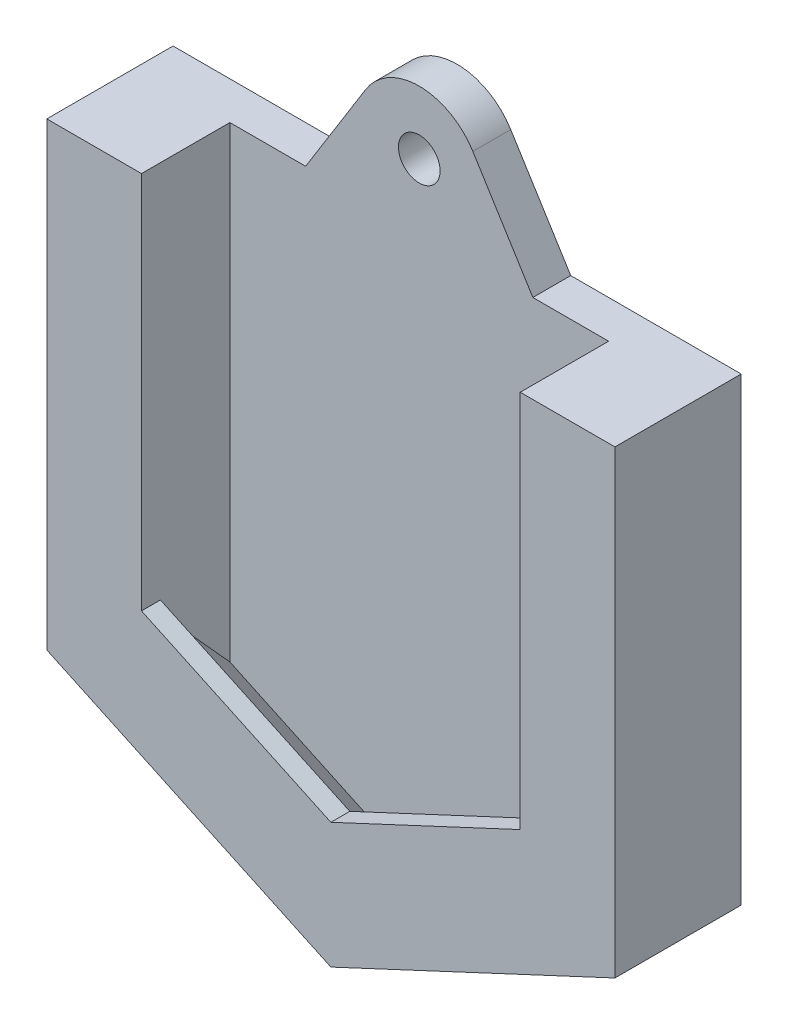
SolidWorks part; units mm, degrees
ref_plane "Plano frontal" through (0, 0, 0) normal (0, 0, 1) x (1, 0, 0)
ref_plane "Plano superior" through (0, 0, 0) normal (0, 1, 0) x (1, 0, 0)
ref_plane "Plano direito" through (0, 0, 0) normal (1, 0, 0) x (0, 0, -1)
sketch "Esboço1" plane through (0, 0, 0) normal (0, 0, 1) x (1, 0, 0)
  line L1 (-22.5, 25) -> (22.5, 25)
  line L2 (-22.5, 25) -> (-22.5, -25)
  line L3 (-22.5, -25) -> (22.5, -25)
  line L4 (22.5, 25) -> (22.5, -25)
  line L5 (-22.5, 25) -> (22.5, -25) construction
  line L6 (-22.5, -25) -> (22.5, 25) construction
  point P0 (0, 0)
  dimension "D1" = 50
  dimension "D2" = 45
extrude "Ressalto-extrusão1" add sketch "Esboço1" along normal blind 10
sketch "Esboço2" plane through (0, 0, 10) normal (0, 0, 1) x (1, 0, 0)
  line L0 (22.5, 25) -> (-22.5, 25) construction
  line L1 (-15, -5) -> (0, -12)
  line L2 (-15, -5) -> (-15, 25)
  line L3 (-15, 25) -> (15, 25)
  line L4 (15, -5) -> (15, 25)
  line L5 (-15, -5) -> (15, 25) construction
  line L6 (-15, 25) -> (15, -5) construction
  line L7 (0, -12) -> (15, -5)
  point P0 (0, 10)
  point P7 (0, 0)
  point P9 (0, 0)
  point P11 (-14.0954, -1.8648)
  dimension "D1" = 30
  dimension "D2" = 30
  dimension "D3" = 7
extrude "Corte-extrusão1" cut sketch "Esboço2" against normal blind 7
sketch "Esboço3" plane through (0, 0, 3) normal (0, 0, 1) x (1, 0, 0)
  line L0 (-15, -5) -> (-15, -12)
  line L1 (-15, -12) -> (0, -19)
  line L2 (0, -19) -> (15, -12)
  line L3 (15, -12) -> (15, -5)
  line L5 (-15, -5) -> (15, -5)
  line L6 (-15, -5) -> (0, -12) construction
  line L7 (-15, -5) -> (0, -12) construction
  point P7 (15, -5)
  point P8 (-15.0391, -5)
  point P12 (-15, -5)
  dimension "D1" = 7
  dimension "D2" = 14
extrude "Corte-extrusão2" cut sketch "Esboço3" along normal blind 5.5
chamfer "Chanfro1" distance 5.5 angle 45 2 edges at (-7.5, -15.5, 8.5) (7.5, -15.5, 8.5)
sketch "Esboço4" plane through (0, 0, 0) normal (0, 0, -1) x (-1, 0, 0)
  line L0 (4.2453, 32.6415) -> (9, 25)
  line L1 (-15, 25) -> (15, 25) construction
  line L2 (9, 25) -> (-9, 25)
  line L3 (-9, 25) -> (-4.2453, 32.6415)
  arc A0 (4.2453, 32.6415) -> (-4.2453, 32.6415) centre (0, 30) ccw
  circle A1 centre (0, 30) radius 1.65
  point P1 (0, 0)
  point P8 (0, 25)
  point P10 (-8.7035, 25)
  point P11 (0, 0)
  dimension "D1" = 5
  dimension "D2" = 3.3
  dimension "D3" = 18
extrude "Ressalto-extrusão2" add sketch "Esboço4" against normal blind 3
sketch "Esboço5" plane through (0, 0, 10) normal (0, 0, 1) x (1, 0, 0)
  line L0 (-22.5, -11.4318) -> (0, -21.9318)
  line L1 (-22.5, 25) -> (-22.5, -25) construction
  line L3 (0, -21.9318) -> (22.5, -11.4318)
  line L4 (22.5, -25) -> (22.5, 25) construction
  line L5 (22.5, -11.4318) -> (22.5, -32.502)
  line L6 (22.5, -32.502) -> (-22.5, -32.502)
  line L7 (-22.5, -32.502) -> (-22.5, -11.4318)
  line L8 (-15, -5) -> (0, -12) construction
  point P4 (0, 0)
  point P5 (0, -21.8695)
  point P13 (0, 0)
  dimension "D1" = 9
extrude "Corte-extrusão3" cut sketch "Esboço5" against normal through all
